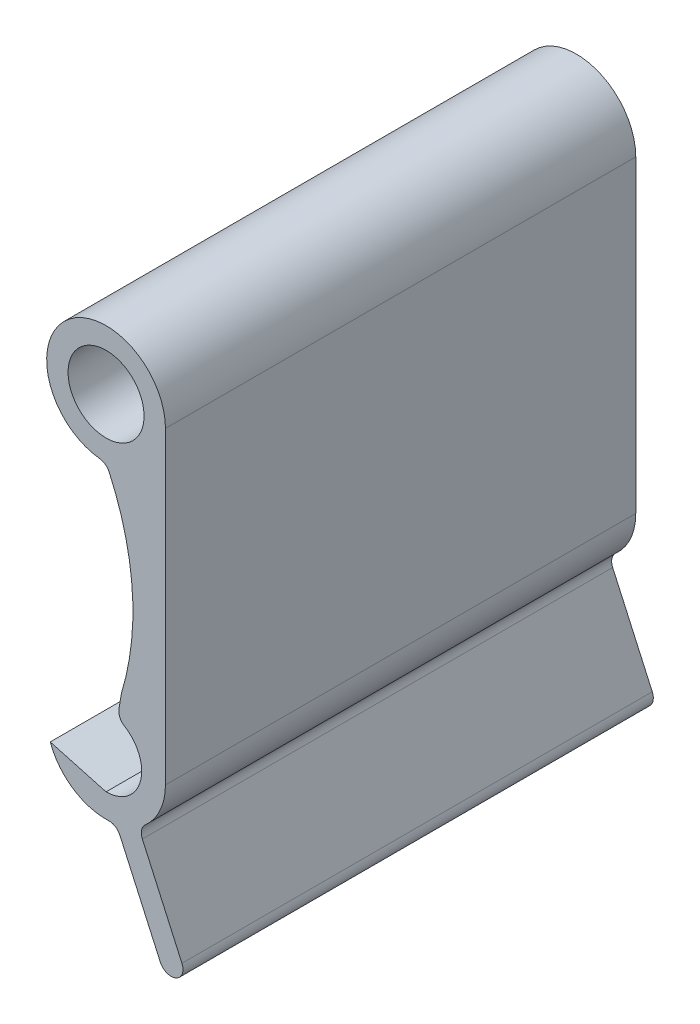
SolidWorks part; units mm, degrees
ref_plane "Front Plane" through (0, 0, 0) normal (0, 0, 1) x (1, 0, 0)
ref_plane "Top Plane" through (0, 0, 0) normal (0, 1, 0) x (1, 0, 0)
ref_plane "Right Plane" through (0, 0, 0) normal (1, 0, 0) x (0, 0, -1)
sketch "Sketch1" plane through (0, 0, 0) normal (0, 0, 1) x (1, 0, 0)
  line L0 (2.5, 0) -> (2.5, -13) construction
  line L1 (0, -14.5) -> (-2.2289, -14.1323)
  line L2 (0, -14.5) -> (0.6458, -10.5849)
  line L3 (0, -14.5) -> (-2.3495, -13.8543)
  circle A0 centre (0, 0) radius 1.6
  circle A1 centre (0, 0) radius 2.5
  arc A2 (-2.2289, -14.1323) -> (0.6458, -10.5849) centre (0, -13) ccw
  arc A3 (-0.4818, -14.4205) -> (0.4818, -11.5795) centre (0, -13) ccw
  arc A4 (0.6458, -10.5849) -> (0, -2.5) centre (-9.8698, -7.3566) ccw
  arc A5 (2.5, 0) -> (2.5, -13) centre (-123.3322, -6.5) cw
  arc A6 (-2.3495, -13.8543) -> (0.6458, -10.5849) centre (0, -13) ccw
  dimension "D1" = 3.2
  dimension "D2" = 5
  dimension "D3" = 3
  dimension "D4" = 5
  dimension "D8" = 11
  dimension "D9" = 126
  dimension "D10" = 6
  dimension "D5" = 0.02
  dimension "D6" = 1.48
  dimension "D7" = 13
extrude "Boss-Extrude1" add sketch "Sketch1" along normal blind 19.8 contours A1 A0 | L0 A1 A4 A2 | A3 L1 A2 L2 | L1 A3 | L3 A6 L1 region at (1.7178, -1.7178, 0) region at (1.6984, -6.2763, 0) region at (0.5663, -15.3649, 0) region at (-1.5286, -14.1617, 0) region at (-0.2422, -14.4682, 0)
fillet "Fillet1" radius 0.5 2 edges at (0, -2.5, 9.9) (0.4818, -11.5795, 9.9)
sketch "Sketch2" plane through (0, 0, 19.8) normal (0, 0, 1) x (1, 0, 0)
  line L0 (1.3649, -15.0945) -> (3.4003, -19.6093)
  line L1 (3.4003, -19.6093) -> (2.4887, -20.0203)
  line L2 (2.4887, -20.0203) -> (0.4337, -15.4621)
  line L3 (0, -14.5) -> (0.4337, -15.4621) construction
  arc A0 (-2.3495, -13.8543) -> (2.5, -13) centre (0, -13) ccw construction
  arc A1 (0.4337, -15.4621) -> (1.3649, -15.0945) centre (0, -13) ccw
  arc M10 (-2.3495, -13.8543) -> (2.5, -13) centre (0, -13) ccw
  dimension "D3" = 2.5
  dimension "D1" = 1
  dimension "D2" = 5
extrude "Boss-Extrude2" add sketch "Sketch2" against normal up to surface (19.8 mm away) contours L2 L1 L0 M10 region at (1.9281, -17.5623, 19.8) up to face at (1.6, 0, 0)
fillet "Fillet2" radius 0.5 4 edges at (0.4337, -15.4621, 9.9) (1.3649, -15.0945, 9.9) (3.4003, -19.6093, 9.9) (2.4887, -20.0203, 9.9)
